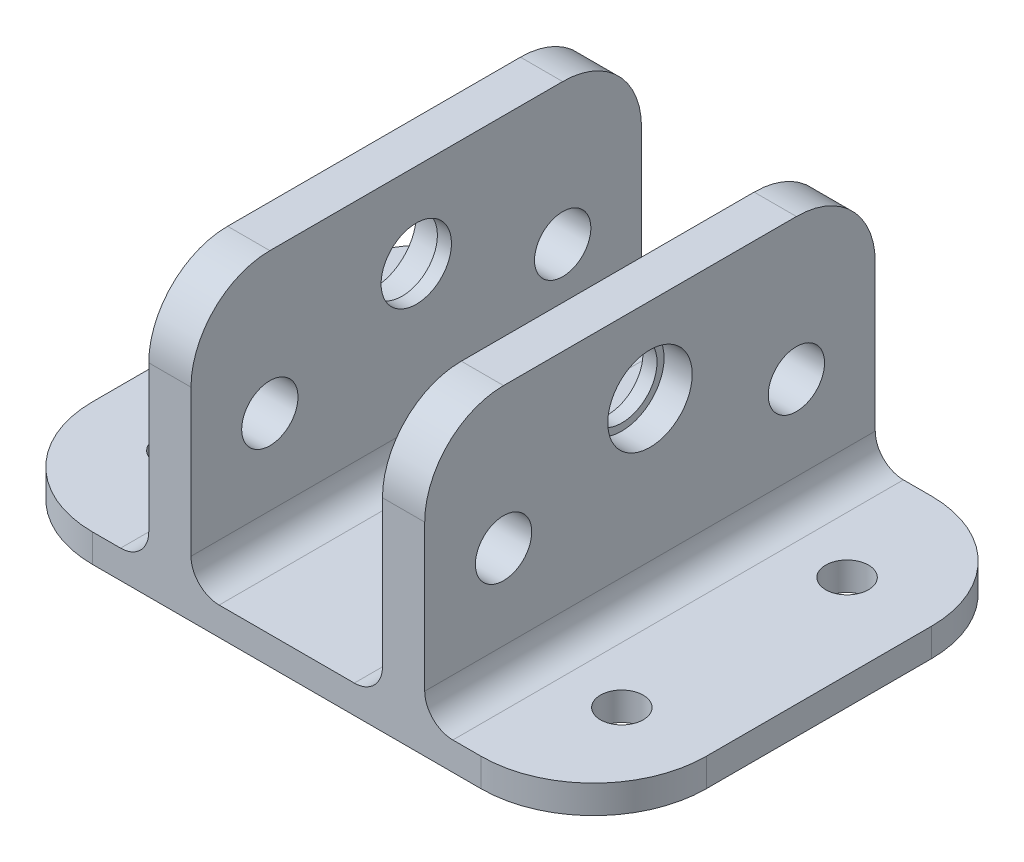
SolidWorks part; units mm, degrees
ref_plane "Front Plane" through (0, 0, 0) normal (0, 0, 1) x (1, 0, 0)
ref_plane "Top Plane" through (0, 0, 0) normal (0, 1, 0) x (1, 0, 0)
ref_plane "Right Plane" through (0, 0, 0) normal (1, 0, 0) x (0, 0, -1)
sketch "Sketch3" plane through (0, 0, 0) normal (0, 0, 1) x (1, 0, 0)
  line L0 (-34.6075, 0) -> (34.6075, 0)
  line L1 (34.6075, 0) -> (34.6075, 3.175)
  line L2 (34.6075, 3.175) -> (15.5575, 3.175)
  line L3 (15.5575, 3.175) -> (15.5575, 31.75)
  line L4 (15.5575, 31.75) -> (10.795, 31.75)
  line L5 (10.795, 31.75) -> (10.795, 3.175)
  line L6 (10.795, 3.175) -> (-10.795, 3.175)
  line L7 (-10.795, 3.175) -> (-10.795, 31.75)
  line L8 (-10.795, 31.75) -> (-15.5575, 31.75)
  line L9 (-15.5575, 31.75) -> (-15.5575, 3.175)
  line L10 (-15.5575, 3.175) -> (-34.6075, 3.175)
  line L11 (-34.6075, 3.175) -> (-34.6075, 0)
  point P15 (0, 0)
  dimension "D1" = 3.175
  dimension "D2" = 4.7625
  dimension "D3" = 28.575
  dimension "D4" = 19.05
  dimension "D5" = 21.59
extrude "Boss-Extrude2" add sketch "Sketch3" along normal blind 50.8
sketch "Sketch4" plane through (-15.5575, 0, 0) normal (-1, 0, 0) x (0, 0, 1)
  line L0 (25.4, 22.225) -> (0, 22.225) construction
  line L1 (8.89, 15.875) -> (0, 15.875) construction
  line L2 (41.91, 15.875) -> (50.8, 15.875) construction
  line L3 (50.8, 0) -> (0, 0) construction
  line L4 (0, 31.75) -> (0, 3.175)
  line L5 (0, 3.175) -> (50.8, 3.175)
  line L6 (50.8, 3.175) -> (50.8, 31.75)
  line L7 (50.8, 31.75) -> (0, 31.75)
  line L8 (0, 31.75) -> (0, 3.175)
  line L9 (0, 3.175) -> (50.8, 3.175)
  line L10 (50.8, 3.175) -> (50.8, 31.75)
  line L11 (50.8, 31.75) -> (0, 31.75)
  line L13 (25.4, 22.225) -> (50.8, 22.225) construction
  line L14 (8.89, 15.875) -> (8.89, 3.175) construction
  line L15 (41.91, 15.875) -> (41.91, 3.175) construction
  circle A0 centre (8.89, 15.875) radius 3.175
  circle A1 centre (41.91, 15.875) radius 3.175
  circle A2 centre (25.4, 22.225) radius 3.9688
  circle A3 centre (25.4, 22.225) radius 4.7625
  point P10 (0, 0)
  point P16 (0, 0)
  dimension "D2" = 6.35
  dimension "D3" = 9.525
  dimension "D4" = 7.9375
  dimension "D5" = 15.875
  dimension "D6" = 8.89
  dimension "D7" = 22.225
  dimension "D1" = 0
extrude "Cut-Extrude1" cut sketch "Sketch4" against normal through all contours A0 | A1 | A2 region at (-15.5575, 15.875, 8.89) region at (-15.5575, 15.875, 41.91) region at (-15.5575, 22.225, 25.4)
sketch "Sketch5" plane through (0, 3.175, 0) normal (0, 1, 0) x (1, 0, 0)
  line L0 (34.6075, 0) -> (15.5575, 0) construction
  line L1 (15.5575, 0) -> (15.5575, -50.8) construction
  line L2 (15.5575, -50.8) -> (34.6075, -50.8) construction
  line L3 (34.6075, -50.8) -> (34.6075, 0) construction
  line L4 (15.5575, 0) -> (10.795, 0) construction
  line L5 (10.795, 0) -> (10.795, -50.8) construction
  line L6 (10.795, -50.8) -> (15.5575, -50.8) construction
  line L7 (15.5575, -50.8) -> (15.5575, 0) construction
  line L8 (10.795, 0) -> (-10.795, 0) construction
  line L9 (-10.795, 0) -> (-10.795, -50.8) construction
  line L10 (-10.795, -50.8) -> (10.795, -50.8) construction
  line L11 (10.795, -50.8) -> (10.795, 0) construction
  line L12 (-10.795, 0) -> (-15.5575, 0) construction
  line L13 (-15.5575, 0) -> (-15.5575, -50.8) construction
  line L14 (-15.5575, -50.8) -> (-10.795, -50.8) construction
  line L15 (-10.795, -50.8) -> (-10.795, 0) construction
  line L16 (-15.5575, 0) -> (-34.6075, 0) construction
  line L17 (-34.6075, 0) -> (-34.6075, -50.8) construction
  line L18 (-34.6075, -50.8) -> (-15.5575, -50.8) construction
  line L19 (-15.5575, -50.8) -> (-15.5575, 0) construction
  line L20 (34.6075, 0) -> (15.5575, 0)
  line L21 (15.5575, 0) -> (15.5575, -50.8)
  line L22 (15.5575, -50.8) -> (34.6075, -50.8)
  line L23 (34.6075, -50.8) -> (34.6075, 0)
  line L24 (15.5575, 0) -> (10.795, 0)
  line L25 (10.795, 0) -> (10.795, -50.8)
  line L26 (10.795, -50.8) -> (15.5575, -50.8)
  line L27 (15.5575, -50.8) -> (15.5575, 0)
  line L28 (10.795, 0) -> (-10.795, 0)
  line L29 (-10.795, 0) -> (-10.795, -50.8)
  line L30 (-10.795, -50.8) -> (10.795, -50.8)
  line L31 (10.795, -50.8) -> (10.795, 0)
  line L32 (-10.795, 0) -> (-15.5575, 0)
  line L33 (-15.5575, 0) -> (-15.5575, -50.8)
  line L34 (-15.5575, -50.8) -> (-10.795, -50.8)
  line L35 (-10.795, -50.8) -> (-10.795, 0)
  line L36 (-15.5575, 0) -> (-34.6075, 0)
  line L37 (-34.6075, 0) -> (-34.6075, -50.8)
  line L38 (-34.6075, -50.8) -> (-15.5575, -50.8)
  line L39 (-15.5575, -50.8) -> (-15.5575, 0)
  line L40 (-25.0825, 0) -> (-25.0825, -12.7) construction
  line L41 (25.0825, 0) -> (25.0825, -12.7) construction
  line L42 (-34.6075, -25.4) -> (34.6075, -25.4) construction
  line L43 (-25.0825, -50.8) -> (-25.0825, -38.1) construction
  line L44 (-25.0825, -12.7) -> (-25.0825, -25.4) construction
  line L45 (-25.0825, -25.4) -> (-25.0825, -38.1) construction
  line L46 (-25.0825, -38.1) -> (-25.0825, -50.8) construction
  line L47 (-25.0825, -12.7) -> (-25.0825, 0) construction
  line L48 (25.0825, -50.8) -> (25.0825, -38.1) construction
  line L49 (25.0825, -12.7) -> (25.0825, -25.4) construction
  line L50 (25.0825, -25.4) -> (25.0825, -38.1) construction
  line L51 (0, 0) -> (0, -50.8) construction
  circle A0 centre (-25.0825, -12.7) radius 2.413
  circle A1 centre (-25.0825, -38.1) radius 2.413
  circle A2 centre (25.0825, -12.7) radius 2.413
  circle A3 centre (25.0825, -38.1) radius 2.413
  point P26 (9.525, -25.4)
  point P31 (9.525, -25.4)
  point P34 (-25.0825, -25.4)
  point P36 (-25.0825, -25.4)
  point P39 (9.525, -25.4)
  dimension "D1" = 4.826
  dimension "D2" = 12.7
extrude "Cut-Extrude2" cut sketch "Sketch5" against normal through all contours A1 | A0 | A2 | A3 region at (-25.0825, 3.175, 12.7) region at (-25.0825, 3.175, 38.1) region at (25.0825, 3.175, 12.7) region at (25.0825, 3.175, 38.1)
extrude "Cut-Extrude3" cut sketch "Sketch4<3>" against normal blind 3.175 contours A3 A2 region at (-15.5575, 22.225, 20.7722)
sketch "Sketch4<3>" plane through (-15.5575, 0, 0) normal (-1, 0, 0) x (0, 0, 1) same geometry as "Sketch4"
sketch "Sketch6" plane through (15.5575, 0, 0) normal (1, 0, 0) x (0, 0, -1)
  line L4 (0, 3.175) -> (0, 31.75)
  line L5 (0, 31.75) -> (-50.8, 31.75)
  line L6 (-50.8, 31.75) -> (-50.8, 3.175)
  line L7 (-50.8, 3.175) -> (0, 3.175)
  line L8 (0, 3.175) -> (0, 31.75)
  line L9 (0, 31.75) -> (-50.8, 31.75)
  line L10 (-50.8, 31.75) -> (-50.8, 3.175)
  line L11 (-50.8, 3.175) -> (0, 3.175)
  circle A0 centre (-25.4, 22.225) radius 4.7625
  circle A1 centre (-25.4, 22.225) radius 3.9688 construction
  circle A2 centre (-25.4, 22.225) radius 3.9688
  circle M8 centre (-25.4, 22.225) radius 3.9688
  dimension "D2" = 9.525
  dimension "D1" = 0
extrude "Cut-Extrude4" cut sketch "Sketch6" against normal blind 3.175 contours A0 M8 region at (15.5575, 22.225, 30.0278)
fillet "Fillet1" radius 12.7 4 edges at (34.6075, 1.5875, 0) (34.6075, 1.5875, 50.8) (-34.6075, 1.5875, 50.8) (-34.6075, 1.5875, 0)
fillet "Fillet2" radius 3.175 4 edges at (15.5575, 3.175, 25.4) (10.795, 3.175, 25.4) (-10.795, 3.175, 25.4) (-15.5575, 3.175, 25.4)
fillet "Fillet3" radius 8.89 4 edges at (-13.1762, 31.75, 50.8) (13.1762, 31.75, 50.8) (13.1762, 31.75, 0) (-13.1762, 31.75, 0)
